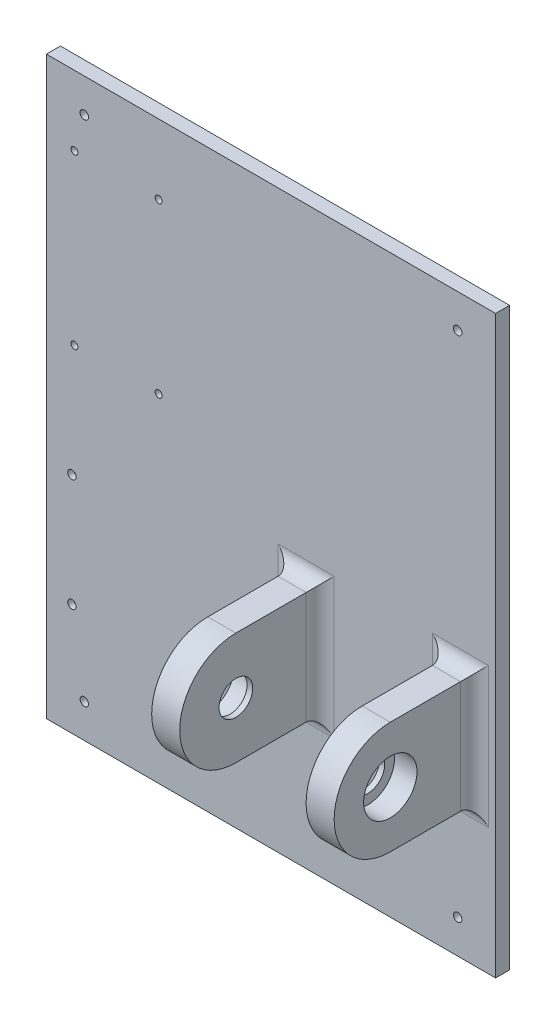
SolidWorks part; units mm, degrees
ref_plane "正面" through (0, 0, 0) normal (0, 0, 1) x (1, 0, 0)
ref_plane "平面" through (0, 0, 0) normal (0, 1, 0) x (1, 0, 0)
ref_plane "右側面" through (0, 0, 0) normal (1, 0, 0) x (0, 0, -1)
sketch "ｽｹｯﾁ2" plane through (0, 0, 0) normal (0, 0, 1) x (1, 0, 0)
  line L0 (-120, 124.8362) -> (-120, -80.1638)
  line L5 (-120, -80.1638) -> (40, -80.1638)
  line L6 (40, -80.1638) -> (40, 124.8362)
  line L7 (40, 124.8362) -> (-120, 124.8362)
  point P0 (0, 0)
  dimension "D1" = 205
  dimension "D2" = 120
  dimension "D3" = 40
extrude "ﾎﾞｽ - 押し出し1" add sketch "ｽｹｯﾁ2" along normal blind 5
sketch "ｽｹｯﾁ3" plane through (0, 0, 0) normal (0, 0, 1) x (1, 0, 0)
  line L0 (-32.5, 10) -> (-32.5, -30)
  line L1 (-32.5, -30) -> (-22.5, -30)
  line L2 (-22.5, -30) -> (-22.5, 10)
  line L3 (-22.5, 10) -> (-32.5, 10)
  dimension "D1" = 10
  dimension "D2" = 40
  dimension "D3" = 30
  dimension "D4" = 22.5
extrude "ﾎﾞｽ - 押し出し2" add sketch "ｽｹｯﾁ3" along normal blind 35
ref_plane "平面1" through (-32.5, 0, 0) normal (-1, 0, 0) x (0, 0, 1)
sketch "ｽｹｯﾁ4" plane through (-32.5, 0, 0) normal (-1, 0, 0) x (0, 0, 1)
  line L0 (35, 10) -> (35, -30) construction
  circle A0 centre (35, -10) radius 20
extrude "ﾎﾞｽ - 押し出し3" add sketch "ｽｹｯﾁ4" against normal blind 10
sketch "ｽｹｯﾁ5" plane through (-32.5, 0, 0) normal (-1, 0, 0) x (0, 0, 1)
  circle A0 centre (35, -10) radius 9.5
  dimension "D1" = 19
extrude "ｶｯﾄ - 押し出し1" cut sketch "ｽｹｯﾁ5" against normal blind 8
sketch "ｽｹｯﾁ13" plane through (-22.5, 0, 0) normal (1, 0, 0) x (0, 0, -1)
  circle A0 centre (-35, -10) radius 6
  dimension "D1" = 12
extrude "ｶｯﾄ - 押し出し2" cut sketch "ｽｹｯﾁ13" against normal through all
fillet "ﾌｨﾚｯﾄ1" radius 5 4 edges at (-27.5, -30, 5) (-32.5, -10, 5) (-27.5, 10, 5) (-22.5, -10, 5)
mirror "ﾐﾗｰ2" about plane through (0, 0, 0) normal (1, 0, 0) of "ﾌｨﾚｯﾄ1", "ｶｯﾄ - 押し出し2", "ｶｯﾄ - 押し出し1", "ﾎﾞｽ - 押し出し3", "ﾎﾞｽ - 押し出し2"
ref_plane "平面2" through (-22.5, 0, 0) normal (1, 0, 0) x (0, 0, -1)
sketch "ｽｹｯﾁ14" plane through (0, 0, 0) normal (0, 0, 1) x (1, 0, 0)
  circle A0 centre (-110.9, -0.35) radius 1.5
  circle A1 centre (-110.9, -40.35) radius 1.5
  dimension "D1" = 3
  dimension "D2" = 3
  dimension "D3" = 110.9
  dimension "D5" = 110.9
  dimension "D4" = 40
  dimension "D6" = 0.35
extrude "ｶｯﾄ - 押し出し3" cut sketch "ｽｹｯﾁ14" along normal blind 10
sketch "ｽｹｯﾁ15" plane through (0, 0, 0) normal (0, 0, 1) x (1, 0, 0)
  line L0 (-110.9, -0.35) -> (-110.9, -40.35) construction
  line L2 (-113.75, -1.9954) -> (-110.9, -3.6409)
  line L3 (-110.9, -3.6409) -> (-108.05, -1.9954)
  line L4 (-108.05, -1.9954) -> (-108.05, 1.2954)
  line L5 (-108.05, 1.2954) -> (-110.9, 2.9409)
  line L6 (-110.9, 2.9409) -> (-113.75, 1.2954)
  line L7 (-113.75, 1.2954) -> (-113.75, -1.9954)
  line L8 (-113.75, -41.9954) -> (-110.9, -43.6409)
  line L9 (-110.9, -43.6409) -> (-108.05, -41.9954)
  line L10 (-108.05, -41.9954) -> (-108.05, -38.7046)
  line L11 (-108.05, -38.7046) -> (-110.9, -37.0591)
  line L12 (-110.9, -37.0591) -> (-113.75, -38.7046)
  line L13 (-113.75, -38.7046) -> (-113.75, -41.9954)
  circle A0 centre (-110.9, -0.35) radius 3.381
  circle A1 centre (-110.9, -40.35) radius 2.85
  circle A2 centre (-110.9, -0.35) radius 2.85 construction
  circle A3 centre (-110.9, -40.35) radius 2.85 construction
  dimension "D1" = 5.7
  dimension "D2" = 5.7
  dimension "D3" = 5.7
extrude "ｶｯﾄ - 押し出し4" cut sketch "ｽｹｯﾁ15" along normal blind 3 contours A1 | L2 L3 L4 L5 L6 L7 | L8 L9 L10 L11 L12 L13
sketch "ｽｹｯﾁ16" plane through (0, 0, 5) normal (0, 0, 1) x (1, 0, 0)
  line L0 (-120, -80.1638) -> (-120, -50.1638)
  line L1 (-120, 124.8362) -> (-120, -80.1638) construction
  line L2 (-120, -50.1638) -> (40, -50.1638)
  line L3 (40, -80.1638) -> (40, 124.8362) construction
  line L4 (40, -50.1638) -> (40, -80.1638)
  line L5 (40, -80.1638) -> (-120, -80.1638)
  dimension "D1" = 30
sketch "ｽｹｯﾁ17" plane through (0, 0, 5) normal (0, 0, 1) x (1, 0, 0)
  line L0 (-106.5, 112.8362) -> (-106.5, -68.1638)
  line L1 (-106.5, -68.1638) -> (26.5, -68.1638)
  line L2 (26.5, -68.1638) -> (26.5, 112.8362)
  line L3 (26.5, 112.8362) -> (-106.5, 112.8362)
  line L4 (40, 124.8362) -> (-120, 124.8362) construction
  line L5 (-120, 124.8362) -> (-120, -80.1638) construction
  dimension "D1" = 133
  dimension "D2" = 181
  dimension "D3" = 12
  dimension "D4" = 13.5
sketch "ｽｹｯﾁ18" plane through (0, 0, 5) normal (0, 0, 1) x (1, 0, 0)
  circle A0 centre (-106.5, 112.8362) radius 1.5
  circle A1 centre (-106.5, -68.1638) radius 1.5
  circle A2 centre (26.5, -68.1638) radius 1.5
  circle A3 centre (26.5, 112.8362) radius 1.5
  dimension "D1" = 3
  dimension "D2" = 3
  dimension "D3" = 3
  dimension "D4" = 3
extrude "ｶｯﾄ - 押し出し5" cut sketch "ｽｹｯﾁ18" against normal through all both contours A1 | A2 | A0 | A3
hole_wizard "M3x0.5 ねじ穴1" positions "ｽｹｯﾁ19" profile "ｽｹｯﾁ20" tap size "M3x0.5" standard "JIS" end condition through all
sketch "ｽｹｯﾁ19" plane through (0, 0, 5) normal (0, 0, 1) x (1, 0, 0)
  point P0 (-110, 100)
  point P2 (-80, 100)
  dimension "D1" = 30
  dimension "D2" = 100
  dimension "D3" = 80
sketch "ｽｹｯﾁ20" plane through (-110, 100, 5) normal (1, 0, 0) x (0, -1, 0)
  line L0 (0, 0) -> (0, 5)
  line L1 (0, 5) -> (1.25, 5)
  line L2 (1.25, 5) -> (1.25, 0)
  line L5 (1.25, 0) -> (0, 0)
  line L11 (0, -6.35) -> (0, 107.95) construction
  dimension "次ｻｰﾌｪｽまでのねじ下穴ﾄﾞﾘﾙ直径" = 2.5
  dimension "次ｻｰﾌｪｽまでのねじ下穴ﾄﾞﾘﾙの深さ" = 5
cosmetic thread "穴のねじ山1" parameters "D2"=3
cosmetic thread "穴のねじ山2" parameters "D2"=3
hole_wizard "M3x0.5 ねじ穴2" positions "ｽｹｯﾁ21" profile "ｽｹｯﾁ22" tap size "M3x0.5" standard "JIS" end condition through all
sketch "ｽｹｯﾁ21" plane through (0, 0, 5) normal (0, 0, 1) x (1, 0, 0)
  point P0 (-80, 40)
  point P2 (-110, 40)
  dimension "D1" = 110
  dimension "D2" = 30
  dimension "D3" = 40
  dimension "D4" = 40
sketch "ｽｹｯﾁ22" plane through (-80, 40, 5) normal (1, 0, 0) x (0, -1, 0)
  line L0 (0, 0) -> (0, 5)
  line L1 (0, 5) -> (1.25, 5)
  line L2 (1.25, 5) -> (1.25, 0)
  line L5 (1.25, 0) -> (0, 0)
  line L11 (0, -6.35) -> (0, 107.95) construction
  dimension "次ｻｰﾌｪｽまでのねじ下穴ﾄﾞﾘﾙ直径" = 2.5
  dimension "次ｻｰﾌｪｽまでのねじ下穴ﾄﾞﾘﾙの深さ" = 5
cosmetic thread "穴のねじ山3" parameters "D2"=3
cosmetic thread "穴のねじ山4" parameters "D2"=3
equation "\"D5@ｽｹｯﾁ14\"=\"D3@ｽｹｯﾁ14\""
